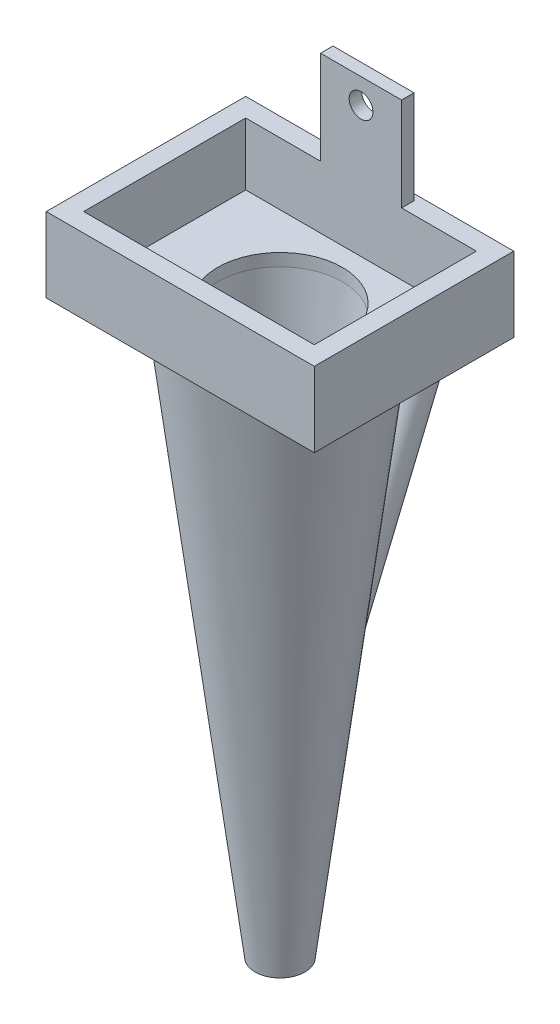
SolidWorks part; units mm, degrees
ref_plane "Front Plane" through (0, 0, 0) normal (0, 0, 1) x (1, 0, 0)
ref_plane "Top Plane" through (0, 0, 0) normal (0, 1, 0) x (1, 0, 0)
ref_plane "Right Plane" through (0, 0, 0) normal (1, 0, 0) x (0, 0, -1)
sketch "Sketch1" plane through (0, 0, 0) normal (0, 1, 0) x (1, 0, 0)
  line L1 (0, 0) -> (37, 0)
  line L2 (0, 0) -> (0, 26)
  line L3 (0, 26) -> (37, 26)
  line L4 (37, 0) -> (37, 26)
  line L5 (-3, -3) -> (40, -3)
  line L6 (-3, -3) -> (-3, 29)
  line L7 (-3, 29) -> (40, 29)
  line L8 (40, -3) -> (40, 29)
  dimension "D1" = 26
  dimension "D2" = 37
  dimension "D3" = 3
  dimension "D4" = 3
  dimension "D5" = 3
  dimension "D6" = 3
extrude "Boss-Extrude1" add sketch "Sketch1" along normal blind 10
sketch "Sketch2" plane through (0, 10, 0) normal (0, 1, 0) x (1, 0, 0)
  line L0 (37, 26) -> (0, 26) construction
  line L1 (25, 26) -> (12, 26)
  line L2 (25, 26) -> (25, 28)
  line L3 (25, 28) -> (12, 28)
  line L4 (12, 26) -> (12, 28)
  line L5 (40, -3) -> (40, 29) construction
  line L6 (-3, 29) -> (-3, -3) construction
  dimension "D1" = 2
  dimension "D2" = 15
  dimension "D3" = 15
extrude "Boss-Extrude2" add sketch "Sketch2" along normal blind 15
sketch "Sketch3" plane through (0, 0, -28) normal (0, 0, -1) x (-1, 0, 0)
  line L0 (-25, 25) -> (-12, 25) construction
  line L1 (-25, 25) -> (-25, 10) construction
  circle A0 centre (-18.5, 21) radius 1.905
  dimension "D1" = 3.81
  dimension "D2" = 4
  dimension "D3" = 6.5
extrude "Cut-Extrude1" cut sketch "Sketch3" against normal up to next
sketch "Sketch4" plane through (0, 0, 0) normal (0, -1, 0) x (1, 0, 0)
  line L1 (40, -29) -> (-3, -29)
  line L2 (40, -29) -> (40, 3)
  line L3 (40, 3) -> (-3, 3)
  line L4 (-3, -29) -> (-3, 3)
extrude "Boss-Extrude3" add sketch "Sketch4" along normal blind 2
sketch "Sketch5" plane through (0, -2, 0) normal (0, -1, 0) x (1, 0, 0)
  line L0 (-3, -29) -> (40, -29) construction
  line L2 (-3, 3) -> (-3, -29) construction
  circle A0 centre (18.5, -13) radius 10
  dimension "D1" = 16
  dimension "D2" = 21.5
extrude "Cut-Extrude2" cut sketch "Sketch5" against normal up to next
sketch "Sketch8" plane through (0, -2, 0) normal (0, -1, 0) x (1, 0, 0)
  line L0 (-3, -13) -> (40, -13) construction
  line L1 (-3, 3) -> (-3, -29) construction
  line L2 (40, -29) -> (40, 3) construction
  point P0 (18.5, -13)
ref_plane "Plane1" through (0, 0, -13) normal (0, 0, 1) x (1, 0, 0)
sketch "Sketch9" plane through (0, 0, -13) normal (0, 0, 1) x (1, 0, 0)
  line L0 (28.5, -2) -> (21.5, -90.9)
  line L1 (21.5, -90.9) -> (22.5, -90.9)
  line L2 (22.5, -90.9) -> (33.5, -2)
  line L3 (33.5, -2) -> (28.5, -2)
  line L4 (-3, -2) -> (40, -2) construction
  dimension "D1" = 1
  dimension "D2" = 3
  dimension "D3" = 88.9
  dimension "D4" = 5
ref_axis "Axis1" through (18.5, -2, -13) along (0, -1, 0)
revolve "Revolve1" add sketch "Sketch9" angle 360 about axis through (18.5, -2, -13) along (0, -1, 0)
sketch "Sketch11" plane through (-3, 0, 0) normal (-1, 0, 0) x (0, 0, 1)
  circle A0 centre (-16.2172, -43.6109) radius 3.175
ref_plane "Plane2" through (18.5, 0, 0) normal (-1, 0, 0) x (0, -1, 0)
sketch "Sketch12" plane through (18.5, 0, 0) normal (-1, 0, 0) x (0, -1, 0)
  line L0 (19.1086, -35.4998) -> (51.8373, -21.8334) construction
  line L2 (2, -28) -> (90.9, -17) construction
  line L3 (2, -28) -> (90.9, -17) construction
ref_axis "Axis2" through (18.5, -19.1086, -35.4998) along (0, -0.9228, 0.3853)
ref_plane "Plane3" through (18.5, -19.1086, -35.4998) normal (0, -0.9228, 0.3853) x (-1, 0, 0)
sketch "Sketch14" plane through (18.5, -19.1086, -35.4998) normal (0, -0.9228, 0.3853) x (-1, 0, 0)
  circle A0 centre (0.3057, 0) radius 3
  dimension "D1" = 6
extrude "Boss-Extrude4" add sketch "Sketch14" along normal blind 45
sketch "Sketch16" plane through (0, -3.6488, 1.5236) normal (0, 0.9228, -0.3853) x (1, 0, 0)
  circle A0 centre (18.1943, 40.1215) radius 2
  circle A1 centre (18.1943, 40.1215) radius 3 construction
  dimension "D1" = 1
extrude "Cut-Extrude3" cut sketch "Sketch16" against normal blind 50
